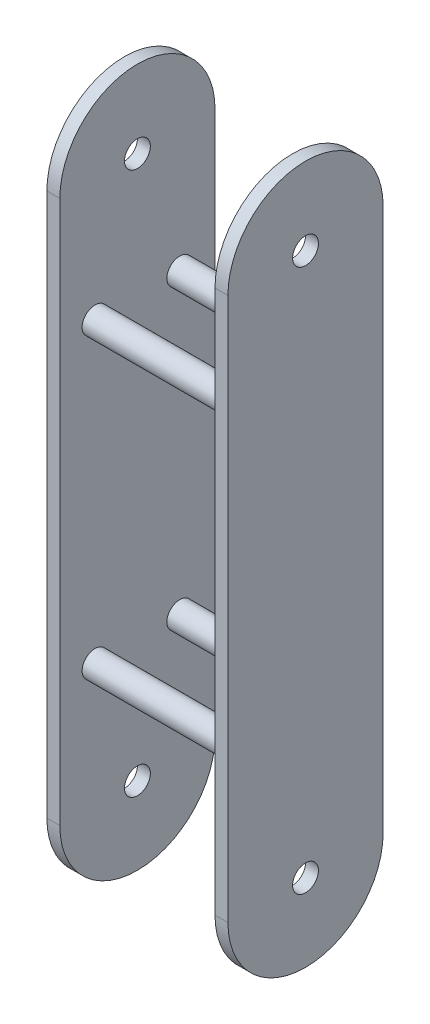
SolidWorks part; units mm, degrees
ref_plane "Front Plane" through (0, 0, 0) normal (0, 0, 1) x (1, 0, 0)
ref_plane "Top Plane" through (0, 0, 0) normal (0, 1, 0) x (1, 0, 0)
ref_plane "Right Plane" through (0, 0, 0) normal (1, 0, 0) x (0, 0, -1)
ref_plane "Plane1" through (35, 0, 0) normal (1, 0, 0) x (0, 0, -1)
sketch "Sketch1" plane through (35, 0, 0) normal (1, 0, 0) x (0, 0, -1)
  line L0 (0, 105) -> (0, -105)
  line L1 (-30, 105) -> (30, 105)
  line L2 (-30, 105) -> (-30, -105)
  line L3 (30, 105) -> (30, -105)
  arc A0 (-30, 105) -> (30, 105) centre (0, 105) cw
  arc A1 (-30, -105) -> (30, -105) centre (0, -105) ccw
  point P4 (0, 0)
  point P8 (0, 105)
  dimension "D1" = 210
  dimension "D2" = 60
extrude "Boss-Extrude1" add sketch "Sketch1" against normal blind 5 contours L2 A1 L3 L1 | A0 L1 region at (35, 117.7324, 0) region at (35, 102.5261, 15)
ref_plane "Plane2" through (-35, 0, 0) normal (1, 0, 0) x (0, 0, -1)
sketch "Sketch2" plane through (-35, 0, 0) normal (1, 0, 0) x (0, 0, -1)
  line L0 (-30, 105) -> (-30, -105) construction
  line L1 (30, 105) -> (30, -105) construction
  line L2 (-30, 105) -> (-30, -105)
  line L3 (30, 105) -> (30, -105)
  arc A0 (-30, -105) -> (30, -105) centre (0, -105) ccw construction
  arc A1 (30, 105) -> (-30, 105) centre (0, 105) ccw construction
  arc A2 (-30, -105) -> (30, -105) centre (0, -105) ccw
  arc A3 (30, 105) -> (-30, 105) centre (0, 105) ccw
extrude "Boss-Extrude2" add sketch "Sketch2" along normal blind 5 separate body
sketch "Sketch3" plane through (35, 0, 0) normal (1, 0, 0) x (0, 0, -1)
  circle A0 centre (0, 105) radius 5
  circle A1 centre (0, -105) radius 5
extrude "Cut-Extrude1" cut sketch "Sketch3" against normal through all
sketch "Sketch4" plane through (35, 0, 0) normal (1, 0, 0) x (0, 0, -1)
  line L0 (0, 38.5) -> (0, -38.5) construction
  line L1 (33, 0) -> (-33, 0) construction
  circle A0 centre (-16.3848, 57.5285) radius 5
  circle A1 centre (16.3848, 57.5285) radius 5
  circle A2 centre (16.3848, -57.5285) radius 5
  circle A3 centre (-16.3848, -57.5285) radius 5
extrude "Boss-Extrude3" add sketch "Sketch4" against normal through all
